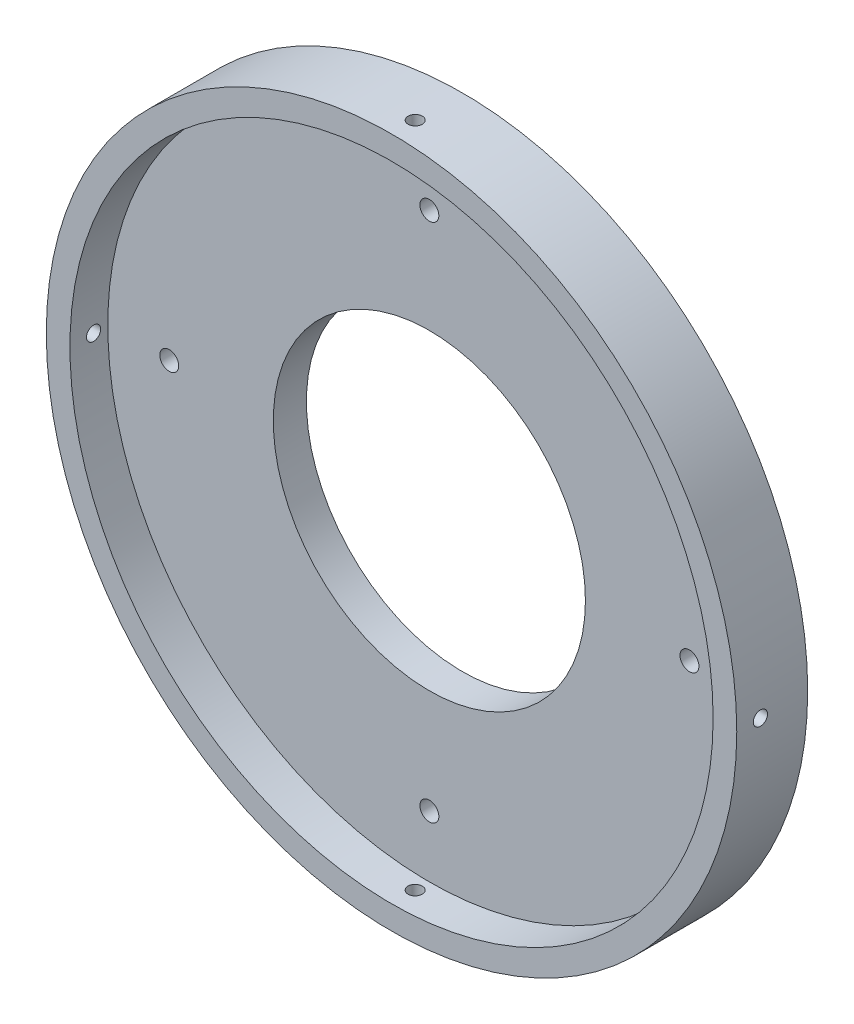
SolidWorks part; units mm, degrees
material "PET"
ref_plane "Front Plane" through (0, 0, 0) normal (0, 0, 1) x (1, 0, 0)
ref_plane "Top Plane" through (0, 0, 0) normal (0, 1, 0) x (1, 0, 0)
ref_plane "Right Plane" through (0, 0, 0) normal (1, 0, 0) x (0, 0, -1)
sketch "Sketch1" plane through (0, 0, 0) normal (0, 0, 1) x (1, 0, 0)
  circle A0 centre (0, 0) radius 73
  circle A1 centre (0, 0) radius 33
  dimension "D1" = 146
  dimension "D2" = 40
extrude "Boss-Extrude1" add sketch "Sketch1" along normal blind 7
sketch "Sketch2" plane through (0, 0, 7) normal (0, 0, 1) x (1, 0, 0)
  circle A0 centre (0, 0) radius 68
  circle A1 centre (0, 0) radius 73
  circle A2 centre (0, 0) radius 73
  dimension "D1" = 0
  dimension "D2" = 5
extrude "Boss-Extrude2" add sketch "Sketch2" along normal blind 8
sketch "Sketch3" plane through (0, 0, 0) normal (0, 1, 0) x (1, 0, 0)
  line L0 (-73, -15) -> (73, -15) construction
  circle A0 centre (0, -10) radius 1.5
  dimension "D2" = 3
  dimension "D1" = 5
extrude "Cut-Extrude1" cut sketch "Sketch3" against normal up to surface (73 mm away) up to face at (73, 0, 0)
pattern_circular "CirPattern1" count 4 over 360 about axis through (0, 0, 7) along (0, 0, -1) of "Cut-Extrude1"
sketch "Sketch9" plane through (0, 0, 0) normal (0, 0, -1) x (-1, 0, 0)
  point P0 (0, 55)
  point P4 (55, 0)
  point P6 (0, -55)
  point P8 (-55, 0)
  dimension "D1" = 55
  dimension "D2" = 0
  dimension "D3" = 55
  dimension "D4" = 55
  dimension "D5" = 55
hole_wizard "Ø4.0mm Dowel Hole1" positions "Sketch9" profile "Sketch10" hole size "Ø4.0" standard "ISO" end condition through all
sketch "Sketch10" plane through (0, 55, 0) normal (1, 0, 0) x (0, 1, 0)
  line L0 (0, 0) -> (0, 15)
  line L1 (0, 15) -> (2, 15)
  line L2 (2, 15) -> (2, 0)
  line L5 (2, 0) -> (0, 0)
  line L11 (0, -6.35) -> (0, 107.95) construction
  dimension "Thru Hole Dia." = 4
  dimension "Thru Hole Depth" = 15
sketch "Sketch13" plane through (0, 0, 0) normal (0, 0, -1) x (-1, 0, 0)
  line L0 (0, 0) -> (55, 0) construction
  line L1 (4.0415, 55) -> (2.0207, 58.5)
  line L2 (2.0207, 58.5) -> (-2.0207, 58.5)
  line L3 (-2.0207, 58.5) -> (-4.0415, 55)
  line L4 (-4.0415, 55) -> (-2.0207, 51.5)
  line L5 (-2.0207, 51.5) -> (2.0207, 51.5)
  line L6 (2.0207, 51.5) -> (4.0415, 55)
  line L7 (55, -4.0415) -> (58.5, -2.0207)
  line L8 (58.5, -2.0207) -> (58.5, 2.0207)
  line L9 (58.5, 2.0207) -> (55, 4.0415)
  line L10 (55, 4.0415) -> (51.5, 2.0207)
  line L11 (51.5, 2.0207) -> (51.5, -2.0207)
  line L12 (51.5, -2.0207) -> (55, -4.0415)
  line L13 (-4.0415, -55) -> (-2.0207, -58.5)
  line L14 (-2.0207, -58.5) -> (2.0207, -58.5)
  line L15 (2.0207, -58.5) -> (4.0415, -55)
  line L16 (4.0415, -55) -> (2.0207, -51.5)
  line L17 (2.0207, -51.5) -> (-2.0207, -51.5)
  line L18 (-2.0207, -51.5) -> (-4.0415, -55)
  line L19 (-55, 4.0415) -> (-58.5, 2.0207)
  line L20 (-58.5, 2.0207) -> (-58.5, -2.0207)
  line L21 (-58.5, -2.0207) -> (-55, -4.0415)
  line L22 (-55, -4.0415) -> (-51.5, -2.0207)
  line L23 (-51.5, -2.0207) -> (-51.5, 2.0207)
  line L24 (-51.5, 2.0207) -> (-55, 4.0415)
  circle A0 centre (0, 55) radius 3.5 construction
  circle A1 centre (55, 0) radius 3.5 construction
  circle A2 centre (0, -55) radius 3.5 construction
  circle A3 centre (-55, 0) radius 3.5 construction
  point P40 (0, 0)
  dimension "D1" = 7
extrude "Cut-Extrude2" cut sketch "Sketch13" against normal blind 3.2
